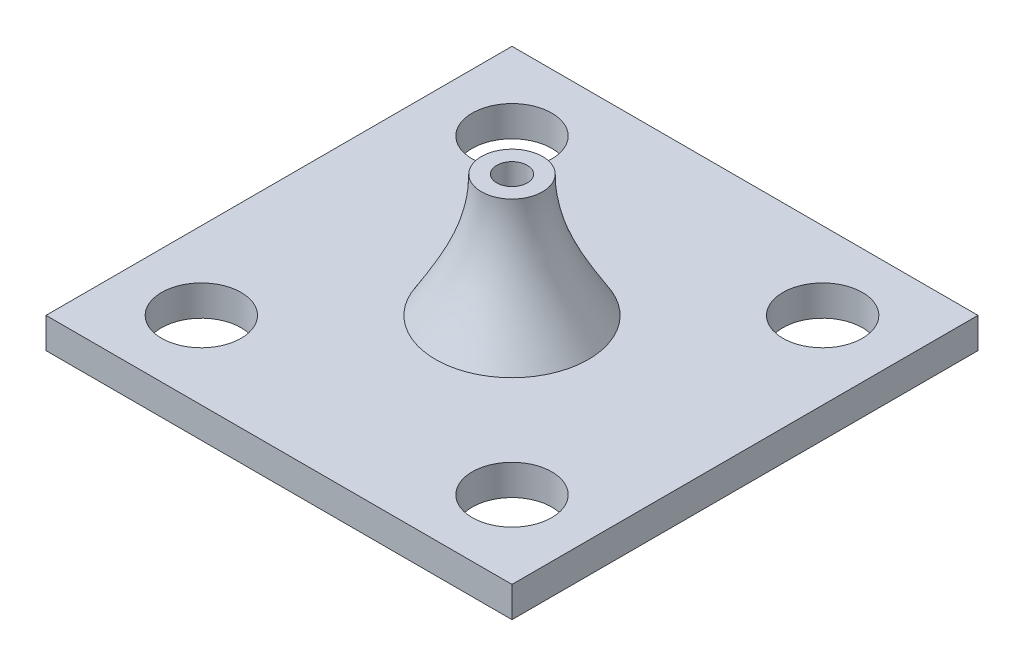
SolidWorks part; units mm, degrees
ref_plane "Front Plane" through (0, 0, 0) normal (0, 0, 1) x (1, 0, 0)
ref_plane "Top Plane" through (0, 0, 0) normal (0, 1, 0) x (1, 0, 0)
ref_plane "Right Plane" through (0, 0, 0) normal (1, 0, 0) x (0, 0, -1)
sketch "Sketch1" plane through (0, 0, 0) normal (0, 1, 0) x (1, 0, 0)
  line L0 (0, -2.7539) -> (0, 5.4568) construction
  line L1 (-19.05, 19.05) -> (19.05, 19.05)
  line L2 (-19.05, 19.05) -> (-19.05, -19.05)
  line L3 (-19.05, -19.05) -> (19.05, -19.05)
  line L4 (19.05, 19.05) -> (19.05, -19.05)
  line L5 (-19.05, 19.05) -> (19.05, -19.05) construction
  line L6 (-19.05, -19.05) -> (19.05, 19.05) construction
  line L7 (-10.9647, 0) -> (8.8737, 0) construction
  circle A0 centre (-12.7, 12.7) radius 3.25
  circle A1 centre (12.7, 12.7) radius 3.25
  circle A2 centre (-12.7, -12.7) radius 3.25
  circle A3 centre (12.7, -12.7) radius 3.25
  point P0 (0, 0)
  dimension "D3" = 6.5
  dimension "D1" = 38.1
  dimension "D2" = 38.1
  dimension "D4" = 6.35
  dimension "D5" = 6.35
extrude "Boss-Extrude1" add sketch "Sketch1" along normal blind 2.5
sketch "Sketch2" plane through (0, 2.5, 0) normal (0, 1, 0) x (1, 0, 0)
  circle A0 centre (0, 0) radius 6.25
  dimension "D1" = 12.5
ref_plane "Plane1" through (0, 12.5, 0) normal (0, 1, 0) x (1, 0, 0)
sketch "Sketch3" plane through (0, 12.5, 0) normal (0, 1, 0) x (1, 0, 0)
  circle A0 centre (0, 0) radius 2.5
  dimension "D1" = 5
ref_plane "Plane2" through (0, 0, 0) normal (1, 0, 0) x (0, 0, -1)
sketch "Sketch4" plane through (0, 0, 0) normal (1, 0, 0) x (0, 0, -1)
  line L0 (2.5, 12.5) -> (-2.5, 12.5) construction
  line L1 (-19.05, 2.5) -> (19.05, 2.5) construction
  line L2 (6.25, 2.5) -> (-6.25, 2.5) construction
  line L3 (0, 13.3143) -> (0, 11.7898) construction
  spline S0 degree 2 poles (2.5, 12.5) (2.4559, 6.9909) (6.25, 2.5) knots 0 0 0 1 1 1
  spline S1 degree 2 poles (-2.5, 12.5) (-2.4559, 6.9909) (-6.25, 2.5) knots 0 0 0 1 1 1
loft "Loft1" add profiles "Sketch3", "Sketch2" start constraint normal to profile start tangent length 1 connector at (2.147, 12.5, -1.2807) connector at (6.1371, 2.5, -1.1827)
sketch "Sketch5" plane through (0, 12.5, 0) normal (0, 1, 0) x (1, 0, 0)
  circle A0 centre (0, 0) radius 1.25
  dimension "D1" = 2.5
extrude "Cut-Extrude1" cut sketch "Sketch5" against normal up to surface (10 mm away) up to face at (12.7, 2.5, 15.95)
